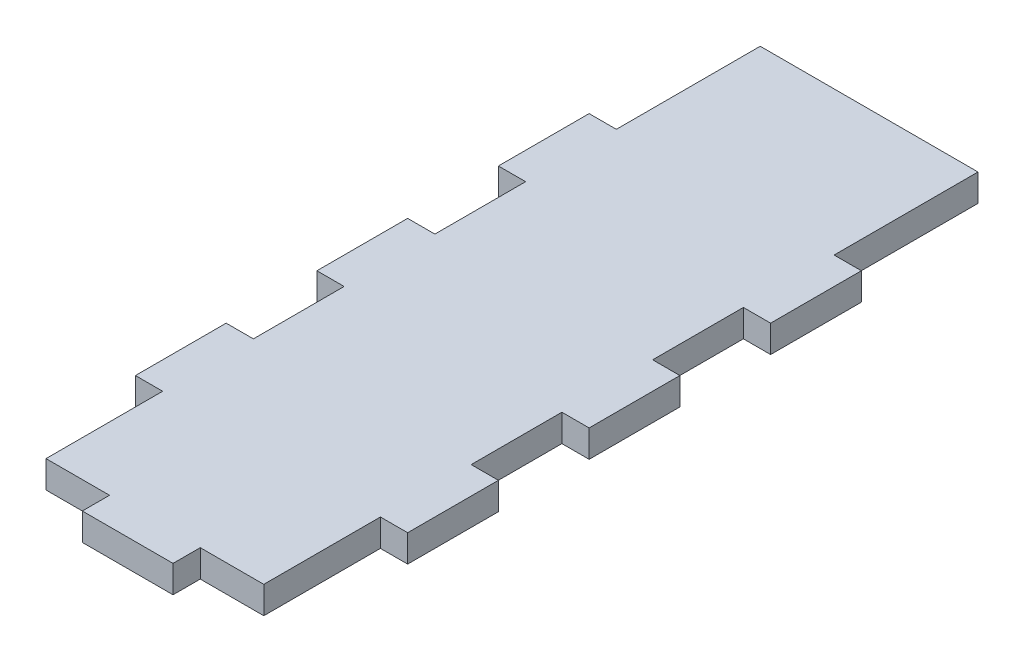
SolidWorks part; units mm, degrees
ref_plane "Alzado" through (0, 0, 0) normal (0, 0, 1) x (1, 0, 0)
ref_plane "Planta" through (0, 0, 0) normal (0, 1, 0) x (1, 0, 0)
ref_plane "Vista lateral" through (0, 0, 0) normal (1, 0, 0) x (0, 0, -1)
sketch "Croquis1" plane through (0, 0, 0) normal (0, 1, 0) x (1, 0, 0)
  line L0 (0, 15.855) -> (0, 25.855)
  line L1 (3, 81.71) -> (27, 81.71)
  line L2 (30, 65.855) -> (30, 55.855)
  line L4 (0, 0) -> (-0.1655, -0.0951)
  line L5 (0, 40.855) -> (0, 45.855)
  line L6 (0, 45.855) -> (3, 45.855)
  line L7 (3, 45.855) -> (3, 55.855)
  line L8 (3, 55.855) -> (0, 55.855)
  line L9 (0, 55.855) -> (0, 65.855)
  line L10 (0, 65.855) -> (3, 65.855)
  line L11 (3, 65.855) -> (3, 81.71)
  line L13 (3, 15.855) -> (3, 3)
  line L14 (0, 15.855) -> (3, 15.855)
  line L15 (3, 25.855) -> (0, 25.855)
  line L16 (3, 35.855) -> (3, 25.855)
  line L17 (0, 35.855) -> (3, 35.855)
  line L21 (30, 35.855) -> (27, 35.855)
  line L22 (27, 35.855) -> (27, 25.855)
  line L23 (27, 25.855) -> (30, 25.855)
  line L24 (30, 15.855) -> (27, 15.855)
  line L25 (27, 15.855) -> (27, 3)
  line L26 (27, 65.855) -> (27, 81.71)
  line L27 (30, 65.855) -> (27, 65.855)
  line L28 (27, 55.855) -> (30, 55.855)
  line L29 (27, 45.855) -> (27, 55.855)
  line L30 (30, 45.855) -> (27, 45.855)
  line L31 (30, 45.855) -> (30, 35.855)
  line L32 (30, 25.855) -> (30, 15.855)
  line L33 (0, 35.855) -> (0, 45.855)
  line L34 (0, 55.855) -> (0, 65.855)
  line L35 (10, 0) -> (20, 0)
  line L36 (10, 0) -> (10, 3)
  line L37 (10, 3) -> (3, 3)
  line L38 (20, 3) -> (27, 3)
  line L39 (20, 0) -> (20, 3)
  dimension "D1" = 3
  dimension "D3" = 5
  dimension "D4" = 3
  dimension "D5" = 10
  dimension "D6" = 10
extrude "Saliente-Extruir1" add sketch "Croquis1" along normal blind 3 contours L33 L17 L16 L15 L0 L14 L13 L25 L24 L32 L23 L22 L21 L31 L30 L29 L28 L2 L27 L26 L1 L11 L10 L9 L8 L7 L6 L5 region at (15, 0, -41.6425)
